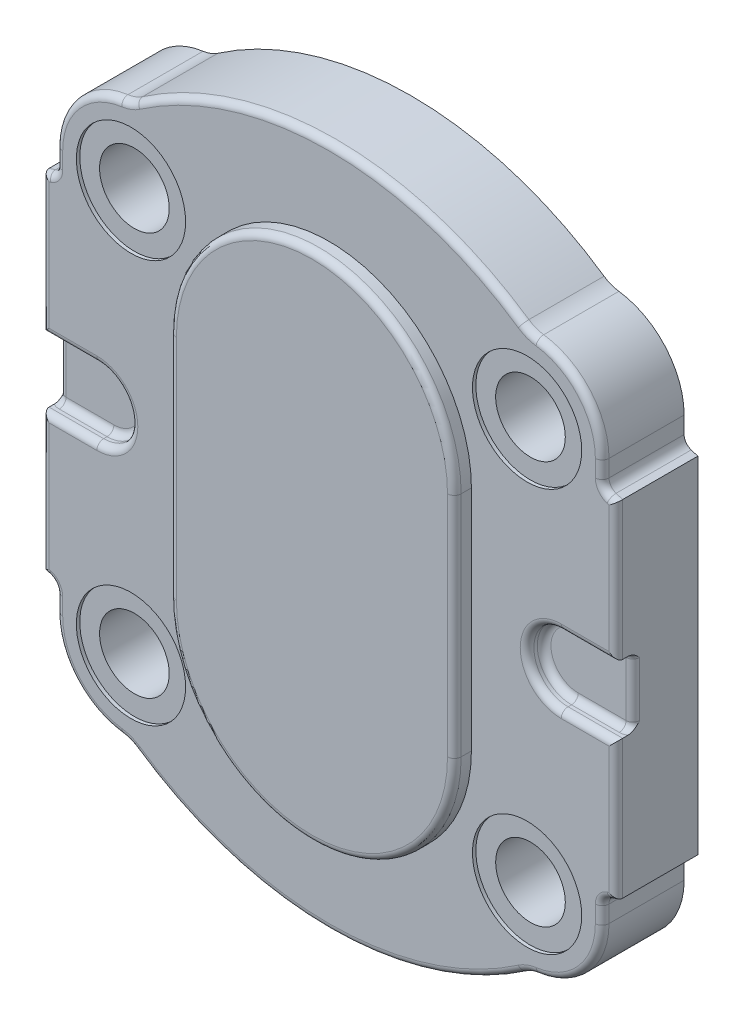
SolidWorks part; units mm, degrees
ref_plane "Front Plane" through (0, 0, 0) normal (0, 0, 1) x (1, 0, 0)
ref_plane "Top Plane" through (0, 0, 0) normal (0, 1, 0) x (1, 0, 0)
ref_plane "Right Plane" through (0, 0, 0) normal (1, 0, 0) x (0, 0, -1)
sketch "Sketch1" plane through (0, 0, 0) normal (0, 0, 1) x (1, 0, 0)
  line L0 (0, 44.3343) -> (0, -58.452) construction
  line L1 (-60.1857, 0) -> (73.3127, 0) construction
  line L2 (-40, 29.5) -> (-40, 27.0192)
  line L3 (-41.0369, 25.5925) -> (-42, 25.2799)
  line L4 (-42, 25.2799) -> (-42, -25.2799)
  line L5 (42, 25.2799) -> (42, -25.2799)
  line L6 (41.0369, 25.5925) -> (42, 25.2799)
  line L7 (40, 29.5) -> (40, 27.0192)
  line L8 (41.0369, -25.5925) -> (42, -25.2799)
  line L9 (40, -29.5) -> (40, -27.0192)
  line L10 (-41.0369, -25.5925) -> (-42, -25.2799)
  line L11 (-40, -29.5) -> (-40, -27.0192)
  arc A0 (28.2748, 41.2375) -> (-28.2748, 41.2375) centre (0, 0) ccw
  circle A1 centre (-29, 29.5) radius 5.1
  circle A2 centre (29, 29.5) radius 5.1
  arc A3 (-30.4453, 40.4046) -> (-40, 29.5) centre (-29, 29.5) ccw
  arc A4 (-28.2748, 41.2375) -> (-30.4453, 40.4046) centre (-31.1023, 45.3613) cw
  arc A5 (-40, 27.0192) -> (-41.0369, 25.5925) centre (-41.5, 27.0192) cw
  arc A6 (40, 27.0192) -> (41.0369, 25.5925) centre (41.5, 27.0192) ccw
  arc A7 (30.4453, 40.4046) -> (40, 29.5) centre (29, 29.5) cw
  arc A8 (28.2748, 41.2375) -> (30.4453, 40.4046) centre (31.1023, 45.3613) ccw
  circle A9 centre (29, -29.5) radius 5.1
  arc A10 (40, -27.0192) -> (41.0369, -25.5925) centre (41.5, -27.0192) cw
  arc A11 (28.2748, -41.2375) -> (30.4453, -40.4046) centre (31.1023, -45.3613) cw
  arc A12 (30.4453, -40.4046) -> (40, -29.5) centre (29, -29.5) ccw
  arc A13 (-40, -27.0192) -> (-41.0369, -25.5925) centre (-41.5, -27.0192) ccw
  arc A14 (-30.4453, -40.4046) -> (-40, -29.5) centre (-29, -29.5) cw
  circle A15 centre (-29, -29.5) radius 5.1
  arc A16 (28.2748, -41.2375) -> (-28.2748, -41.2375) centre (0, 0) cw
  arc A17 (-28.2748, -41.2375) -> (-30.4453, -40.4046) centre (-31.1023, -45.3613) ccw
  point P33 (42, 0)
  point P41 (-42, 0)
  dimension "D1" = 10.2
  dimension "D4" = 50
  dimension "D6" = 11
  dimension "D7" = 5
  dimension "D8" = 42
  dimension "D9" = 1.5
  dimension "D2" = 58
  dimension "D5" = 29.5
extrude "Boss-Extrude1" add sketch "Sketch1" along normal blind 12
sketch "Sketch2" plane through (0, 0, 12) normal (0, 0, 1) x (1, 0, 0)
  line L0 (0, 26.0476) -> (0, -26.0476) construction
  line L1 (-23.4643, 0) -> (27.3392, 0) construction
  line L2 (20.85, 16.68) -> (20.85, -16.68)
  line L3 (-20.85, 16.68) -> (-20.85, -16.68)
  arc A0 (20.85, 16.68) -> (-20.85, 16.68) centre (0, 16.68) ccw
  arc A1 (20.85, -16.68) -> (-20.85, -16.68) centre (0, -16.68) cw
  dimension "D1" = 41.7
  dimension "D2" = 16.68
extrude "Boss-Extrude2" add sketch "Sketch2" along normal blind 2.5
sketch "Sketch3" plane through (0, 0, 12) normal (0, 0, 1) x (1, 0, 0)
  line L0 (0, 24.9712) -> (0, -22.388) construction
  line L1 (-42, 0) -> (17.6486, 0) construction
  line L2 (-42, 25.2799) -> (-42, -25.2799) construction
  line L3 (-34, -5) -> (-46.2863, -5)
  line L4 (-46.2863, -5) -> (-46.2863, 5)
  line L5 (-46.2863, 5) -> (-34, 5)
  line L6 (46.2863, -5) -> (46.2863, 5)
  line L7 (46.2863, 5) -> (34, 5)
  line L8 (34, -5) -> (46.2863, -5)
  arc A0 (-34, -5) -> (-34, 5) centre (-34, 0) ccw
  arc A1 (34, -5) -> (34, 5) centre (34, 0) cw
  dimension "D2" = 10
  dimension "D1" = 8
extrude "Cut-Extrude1" cut sketch "Sketch3" against normal blind 2.5
sketch "Sketch4" plane through (0, 0, 12) normal (0, 0, 1) x (1, 0, 0)
  circle A0 centre (-29, 29.5) radius 8
  circle A1 centre (29, 29.5) radius 8
  circle A2 centre (29, -29.5) radius 8
  circle A3 centre (-29, -29.5) radius 8
  dimension "D1" = 16
extrude "Cut-Extrude3" cut sketch "Sketch4" against normal blind 0.5
fillet "Fillet1" radius 1 38 edges at (0, 37.53, 14.5) (20.85, 0, 14.5) (0, -37.53, 14.5) (-38, 5, 12) (-42, 15.1399, 12) (-41.5184, 25.4362, 12) (-40.2866, 26.1374, 12) (-40, 28.2596, 12) (-37.2734, 36.7492, 12) (-29.311, 40.6932, 12) (0, 50, 12) (29.311, 40.6932, 12) (37.2734, 36.7492, 12) (40, 28.2596, 12) (40.2866, 26.1374, 12) (41.5184, 25.4362, 12) (42, 15.1399, 12) (38, 5, 12) (29, 0, 12) (38, -5, 12) (42, -15.1399, 12) (41.5184, -25.4362, 12) (40.2866, -26.1374, 12) (40, -28.2596, 12) (37.2734, -36.7492, 12) (29.311, -40.6932, 12) (0, -50, 12) (-29.311, -40.6932, 12) (-37.2734, -36.7492, 12) (-40, -28.2596, 12) (-40.2866, -26.1374, 12) (-41.5184, -25.4362, 12) (-42, -15.1399, 12) (-38, -5, 12) (-29, 0, 12) (-42, 0, 9.5) (42, 0, 9.5) (-20.85, 0, 14.5)
fillet "Fillet2" radius 1 5 edges at (-41.7071, -5, 9.2071) (-41.7071, 5, 9.2071) (-29, 0, 9.5) (-37.5, -5, 9.5) (-37.5, 5, 9.5)
fillet "Fillet3" radius 1 5 edges at (41.7071, 5, 9.2071) (41.7071, -5, 9.2071) (29, 0, 9.5) (37.5, 5, 9.5) (37.5, -5, 9.5)
hole_wizard "Ø4.0 (4) Diameter Hole2" positions "Sketch9" profile "Sketch10" hole size "Ø4.0" standard "ISO"
sketch "Sketch9" plane through (0, 0, 0) normal (0, 0, -1) x (-1, 0, 0)
  point P0 (0, 45)
  point P2 (0, -45)
  dimension "D1" = 45
  dimension "D2" = 45
sketch "Sketch10" plane through (0, 45, 0) normal (1, 0, 0) x (0, 1, 0)
  line L0 (0, 0) -> (0, 4.2017)
  line L1 (0, 4.2017) -> (2, 3)
  line L2 (2, 3) -> (2, 0)
  line L5 (2, 0) -> (0, 0)
  line L10 (0, 4.2017) -> (-2, 3) construction
  line L11 (0, -6.35) -> (0, 107.95) construction
  dimension "Hole Dia." = 4
  dimension "Hole Depth" = 3
  dimension "Drill Angle" = 118
